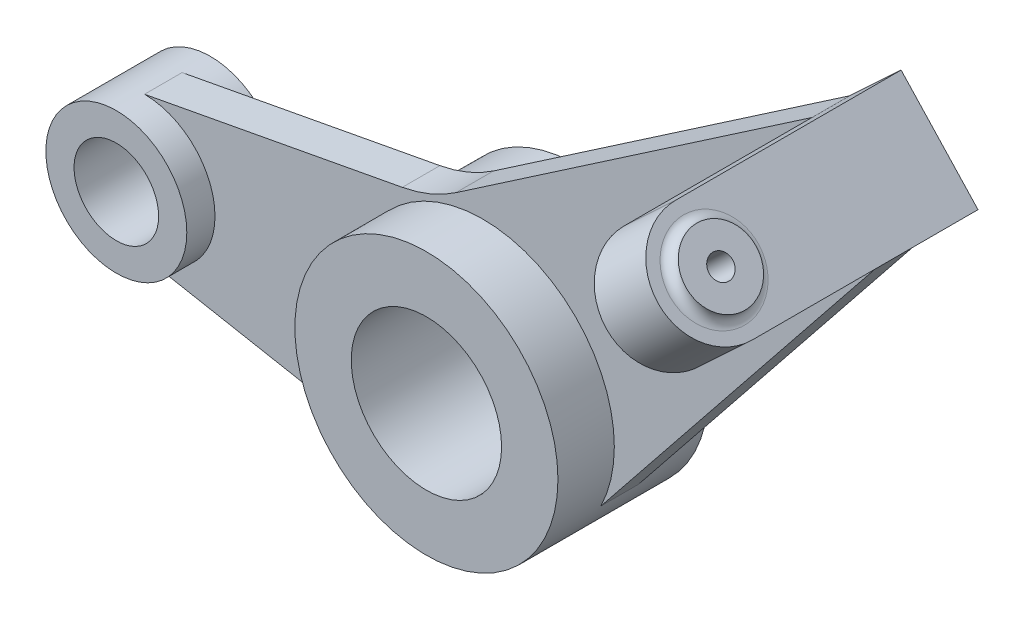
SolidWorks part; units mm, degrees
ref_plane "Front Plane" through (0, 0, 0) normal (0, 0, 1) x (1, 0, 0)
ref_plane "Top Plane" through (0, 0, 0) normal (0, 1, 0) x (1, 0, 0)
ref_plane "Right Plane" through (0, 0, 0) normal (1, 0, 0) x (0, 0, -1)
sketch "Sketch1" plane through (0, 0, 0) normal (0, 0, 1) x (1, 0, 0)
  circle A0 centre (0, 0) radius 28
  circle A1 centre (0, 0) radius 16
  dimension "D1" = 56
  dimension "D2" = 32
extrude "Boss-Extrude1" add sketch "Sketch1" along normal mid plane 32
sketch "Sketch2" plane through (0, 0, 0) normal (0, 0, 1) x (1, 0, 0)
  line L0 (0, 0) -> (-87, 0) construction
  circle A2 centre (0, 0) radius 28 construction
  circle A3 centre (-72, 0) radius 15
  circle A4 centre (-72, 0) radius 9
  dimension "D2" = 30
  dimension "D3" = 18
  dimension "D1" = 115
extrude "Boss-Extrude2" add sketch "Sketch2" along normal mid plane 20 separate body
sketch "Sketch3" plane through (0, 0, 0) normal (0, 0, 1) x (1, 0, 0)
  line L0 (-72, 15) -> (-5.1553, 27.5213)
  line L1 (0, 0) -> (-72, 0) construction
  line L2 (-72, -15) -> (-5.1553, -27.5213)
  circle A0 centre (-72, 0) radius 15 construction
  circle A1 centre (0, 0) radius 28 construction
  arc A2 (-5.1553, 27.5213) -> (-5.1553, -27.5213) centre (0, 0) ccw
  arc A3 (-72, -15) -> (-72, 15) centre (-72, 0) ccw
extrude "Boss-Extrude3" add sketch "Sketch3" along normal mid plane 8
sketch "Sketch4" plane through (0, 0, 0) normal (0, 0, 1) x (1, 0, 0)
  line L0 (0, 0) -> (111.7042, 0) construction
  line L1 (0, 0) -> (89.2252, 83.2038) construction
  line L2 (70.0709, 81.7501) -> (86.4388, 64.1976)
  line L3 (70.0709, 81.7501) -> (-10.9339, 26.4389)
  line L4 (-5.1553, 27.5213) -> (-72, 15) construction
  line L5 (-5.1553, 27.5213) -> (-10.9339, 26.4389)
  line L6 (86.4388, 64.1976) -> (25.123, -12.3627)
  line L7 (-72, 0) -> (0, 0) construction
  arc A2 (-5.1553, 27.5213) -> (-5.1553, -27.5213) centre (0, 0) ccw construction
  circle A3 centre (0, 0) radius 28 construction
  arc A4 (25.123, -12.3627) -> (-5.1553, 27.5213) centre (0, 0) ccw
  dimension "D1" = 137
  dimension "D2" = 150
  dimension "D3" = 15
  dimension "D4" = 24
extrude "Boss-Extrude4" add sketch "Sketch4" along normal mid plane 8
sketch "Sketch5" plane through (0, 0, -4) normal (0, 0, -1) x (-1, 0, 0)
  line L0 (-70.0709, 81.7501) -> (-81.0412, 91.98)
  line L1 (0, 0) -> (-89.2252, 83.2038) construction
  line L2 (-86.4388, 64.1976) -> (-97.4091, 74.4276)
  line L3 (-81.0412, 91.98) -> (-97.4091, 74.4276)
  line L4 (-70.0709, 81.7501) -> (-86.4388, 64.1976) construction
  line L5 (-70.0709, 81.7501) -> (-86.4388, 64.1976)
  dimension "D1" = 15
extrude "Boss-Extrude5" add sketch "Sketch5" against normal blind 60
sketch "Sketch6" plane through (89.2252, 83.2038, 0) normal (0.7314, 0.682, 0) x (0, 0, -1)
  line L0 (-56, 12) -> (4, 12) construction
  line L1 (-56, 12) -> (-56, -12) construction
  line L2 (-56, -12) -> (4, -12) construction
  line L3 (-56, -12) -> (-44, -12)
  line L4 (-56, 12) -> (-56, -12)
  line L5 (-56, 12) -> (-44, 12)
  arc A0 (-44, 12) -> (-44, -12) centre (-44, 0) ccw
  line M2 (4, 12) -> (-56, 12)
  line M3 (-56, 12) -> (-56, -12)
  line M4 (-56, -12) -> (4, -12)
  dimension "D1" = 24
extrude "Cut-Extrude1" cut sketch "Sketch6" against normal through all contours A0 M2 M3 | A0 L4 M4 region at (95.5811, 76.3879, 53.3196) region at (82.8692, 90.0197, 53.3196)
hole_wizard "Hole1" positions "Sketch7" profile "Sketch8" legacy end condition through all
sketch "Sketch7" plane through (78.2548, 72.9738, 0) normal (-0.7314, -0.682, 0) x (0, 0, 1)
  point P0 (44, 0)
sketch "Sketch8" plane through (78.2548, 72.9738, 44) normal (0, 0, 1) x (0.682, -0.7314, 0)
  line L0 (0, 0) -> (0, 26.9708)
  line L1 (0, 26.9708) -> (2.5, 26.9708)
  line L2 (2.5, 26.9708) -> (2.5, 6)
  line L3 (2.5, 6) -> (6, 6)
  line L4 (6, 6) -> (6, 0)
  line L5 (6, 0) -> (0, 0)
  line L6 (0, 110) -> (0, -10) construction
  dimension "Diameter" = 5
  dimension "Depth" = 26.9708
  dimension "C-Bore Diameter" = 12
  dimension "C-Bore Depth" = 6
sketch "Sketch9" plane through (89.2252, 83.2038, 0) normal (0.7314, 0.682, 0) x (0, 0, -1)
  circle A0 centre (-44, 0) radius 7.5
  circle A1 centre (-44, 0) radius 2.5 construction
  circle A2 centre (-44, 0) radius 2.5
  dimension "D1" = 15
extrude "Boss-Extrude6" add sketch "Sketch9" along normal blind 2
fillet "Fillet1" radius 30 1 edges at (-10.9339, 26.4389, 0)
fillet "Fillet2" radius 2 1 edges at (84.1102, 88.689, 44)
